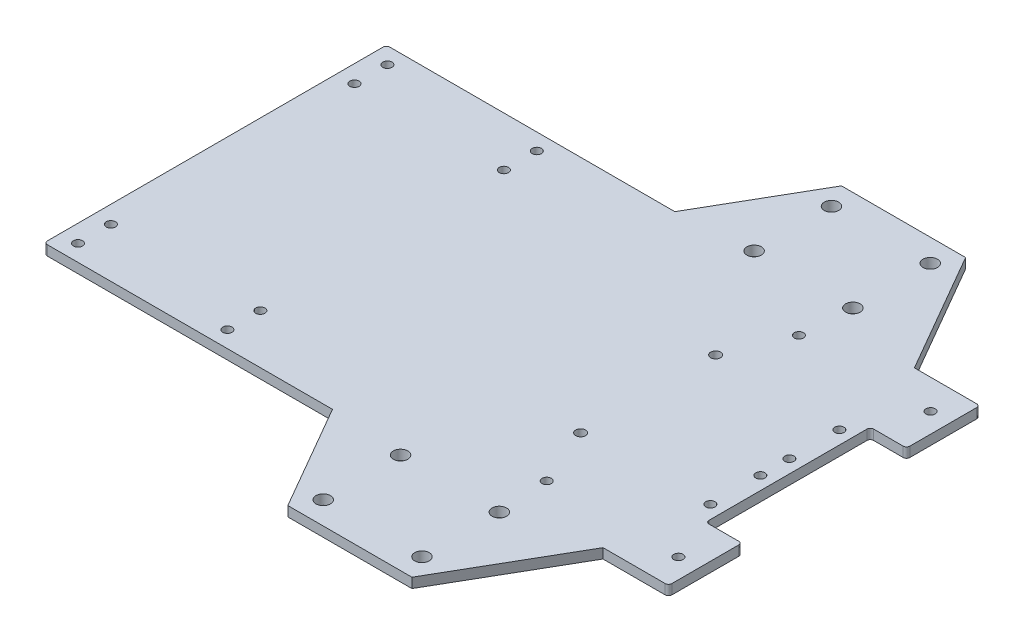
SolidWorks part; units mm, degrees
material "Acrylic (Medium-high impact)"
ref_plane "Front Plane" through (0, 0, 0) normal (0, 0, 1) x (1, 0, 0)
ref_plane "Top Plane" through (0, 0, 0) normal (0, 1, 0) x (1, 0, 0)
ref_plane "Right Plane" through (0, 0, 0) normal (1, 0, 0) x (0, 0, -1)
sketch "Sketch1" plane through (0, 0, 0) normal (0, 1, 0) x (1, 0, 0)
  line L0 (0, 52) -> (0, -52)
  line L12 (0, 52) -> (87.6171, 52)
  line L13 (87.6171, 52) -> (106.15, 84.1)
  line L14 (106.15, 84.1) -> (143.85, 84.1)
  line L15 (143.85, 84.1) -> (165.0965, 47.3)
  line L16 (165.0965, 47.3) -> (185, 47.3)
  line L17 (185, 47.3) -> (185, -47.3)
  line L18 (185, -47.3) -> (165.0965, -47.3)
  line L19 (165.0965, -47.3) -> (143.85, -84.1)
  line L20 (143.85, -84.1) -> (106.15, -84.1)
  line L21 (106.15, -84.1) -> (87.6171, -52)
  line L22 (87.6171, -52) -> (0, -52)
  line L23 (125, 84.1) -> (125, -84.1) construction
  point P12 (125, 0)
  point P13 (141.2253, -84.93)
  point P14 (0, 0)
  point P15 (0, 0)
  point P19 (0, 0)
  point P20 (0, 0)
  point P21 (214.4864, 51.0345)
  point P22 (253.3288, 36.9316)
  point P23 (185, 0)
  point P24 (140.5191, 84.1)
  point P25 (0, 0)
  dimension "D1" = 104
  dimension "D2" = 37.7
  dimension "D3" = 32.1
  dimension "D4" = 120
  dimension "D5" = 143.85
  dimension "D6" = 185
  dimension "D7" = 94.6
extrude "Boss-Extrude1" add sketch "Sketch1" along normal blind 3
sketch "Sketch2" plane through (0, 3, 0) normal (0, 1, 0) x (1, 0, 0)
  line L0 (87.6171, 52) -> (0, 52) construction
  line L1 (0, 52) -> (0, -52) construction
  circle A0 centre (5.3, 47) radius 1.4
  circle A1 centre (5.3, 37) radius 1.4
  circle A2 centre (50.7, 47) radius 1.4
  circle A3 centre (50.7, 37) radius 1.4
  point P8 (0, 0)
  point P11 (0, 0)
  dimension "D3" = 2.8
  dimension "D1" = 5
  dimension "D2" = 5.3
  dimension "D4" = 10
  dimension "D5" = 45.4
extrude "Motor Clevis Holes" cut sketch "Sketch2" against normal through all
mirror "Motor Clevis Holes Mirror" about plane through (0, 0, 0) normal (0, 0, 1) of "Motor Clevis Holes"
sketch "Sketch3" plane through (0, 3, 0) normal (0, 1, 0) x (1, 0, 0)
  line L0 (165.0965, -47.3) -> (185, -47.3) construction
  line L1 (185, -47.3) -> (185, 47.3) construction
  circle A0 centre (179, -38.3) radius 1.4
  circle A1 centre (139, -38.3) radius 1.4
  point P8 (0, 0)
  dimension "D1" = 2.8
  dimension "D2" = 9
  dimension "D3" = 6
  dimension "D4" = 40
extrude "Servo Clevis Holes" cut sketch "Sketch3" against normal through all
mirror "Servo Clevis Holes Mirror" about plane through (0, 0, 0) normal (0, 0, 1) of "Servo Clevis Holes"
sketch "Sketch4" plane through (0, 3, 0) normal (0, 1, 0) x (1, 0, 0)
  line L0 (0, 52) -> (0, -52) construction
  line L1 (0, -52) -> (87.6171, -52) construction
  circle A0 centre (131.57, -20.48) radius 1.5 construction
  circle A1 centre (131.5, -20.5) radius 1.5
  dimension "D3" = 3
  dimension "D6" = 3
  dimension "D1" = 131.57
  dimension "D2" = 31.52
  dimension "D4" = 131.5
  dimension "D5" = 31.5
extrude "Bucket Hole" cut sketch "Sketch4" against normal through all
mirror "Bucket Hole Mirror" about plane through (0, 0, 0) normal (0, 0, 1) of "Bucket Hole"
sketch "Sketch5" plane through (0, 3, 0) normal (0, 1, 0) x (1, 0, 0)
  line L0 (0, -52) -> (87.6171, -52) construction
  line L1 (0, 52) -> (0, -52) construction
  circle A0 centre (110, -53.7) radius 2.2
  circle A1 centre (110, -77.2) radius 2.2
  circle A2 centre (140, -77.2) radius 2.2
  circle A3 centre (140, -53.7) radius 2.2
  point P8 (0, 0)
  point P14 (0, 0)
  dimension "D3" = 4.4
  dimension "D1" = 1.7
  dimension "D2" = 110
  dimension "D4" = 23.5
  dimension "D5" = 30
extrude "Caster Holes" cut sketch "Sketch5" against normal through all
mirror "Caster Holes Mirror" about plane through (0, 0, 0) normal (0, 0, 1) of "Caster Holes"
sketch "Sketch6" plane through (0, 3, 0) normal (0, 1, 0) x (1, 0, 0)
  line L0 (170, 4.4) -> (170, -4.4) construction
  line L1 (185, -47.3) -> (185, 47.3) construction
  line L3 (185, 25) -> (174, 25)
  line L4 (185, 25) -> (185, -25)
  line L5 (185, -25) -> (174, -25)
  line L6 (174, 25) -> (174, -25)
  circle A0 centre (170, 4.4) radius 1.4
  circle A1 centre (170, 19.6) radius 1.4
  circle A2 centre (170, -4.4) radius 1.4
  circle A3 centre (170, -19.6) radius 1.4
  point P8 (185, 0)
  point P11 (170, 0)
  point P16 (185, 0)
  dimension "D1" = 2.8
  dimension "D2" = 15.2
  dimension "D3" = 8.8
  dimension "D4" = 15.2
  dimension "D5" = 15
  dimension "D6" = 4
  dimension "D7" = 50
extrude "Color Sensor Holes" cut sketch "Sketch6" against normal through all
fillet "Fillet2" radius 1 8 edges at (185, 1.5, 47.3) (185, 1.5, 25) (174, 1.5, 25) (174, 1.5, -25) (185, 1.5, -25) (185, 1.5, -47.3) (0, 1.5, -52) (0, 1.5, 52)
